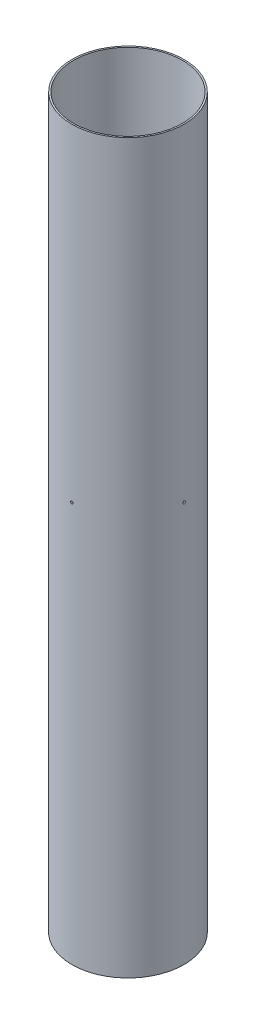
SolidWorks part; units mm, degrees
material "A-Glass Fiber"
ref_plane "Front Plane" through (0, 0, 0) normal (0, 0, 1) x (1, 0, 0)
ref_plane "Top Plane" through (0, 0, 0) normal (0, 1, 0) x (1, 0, 0)
ref_plane "Right Plane" through (0, 0, 0) normal (1, 0, 0) x (0, 0, -1)
sketch "Sketch1" plane through (0, 0, 0) normal (0, 1, 0) x (1, 0, 0)
  circle A0 centre (0, 0) radius 76.1746
  circle A1 centre (0, 0) radius 78.359
  dimension "D1" = 156.718
  dimension "D2" = 152.3492
extrude "Boss-Extrude1" add sketch "Sketch1" along normal blind 1016
ref_axis "Axis1" through (0, 1016, 0) along (0, -1, 0)
sketch "Sketch3" plane through (0, 0, 0) normal (0, 0, 1) x (1, 0, 0)
  line L0 (0, 558.8) -> (0, 1016) construction
  line L1 (78.359, 1016) -> (-78.359, 1016) construction
  circle A0 centre (0, 558.8) radius 1.75
  dimension "D2" = 3.5
  dimension "D1" = 457.2
extrude "Cut-Extrude1" cut sketch "Sketch3" against normal through all
pattern_circular "CirPattern1" count 4 over 360 about axis through (0, 1016, 0) along (0, -1, 0) of "Cut-Extrude1"
equation "\"Fwd_Tube_Length\"= 40in"
equation "\"D1@Boss-Extrude1\" = \"Fwd_Tube_Length\""
equation "\"BKHD_Screw_Diam\"= 3.5mm"
equation "\"Fwd_BKHD_From_Top\"= 18in"
equation "\"D2@Sketch3\"=\"BKHD_Screw_Diam\""
equation "\"D1@Sketch3\"=\"Fwd_BKHD_From_Top\""
equation "\"Bodytube_OD\"= 6.17in"
equation "\"Bodytube_ID\"= 5.998in"
equation "\"D2@Sketch1\"=\"Bodytube_ID\""
equation "\"D1@Sketch1\"=\"Bodytube_OD\""
